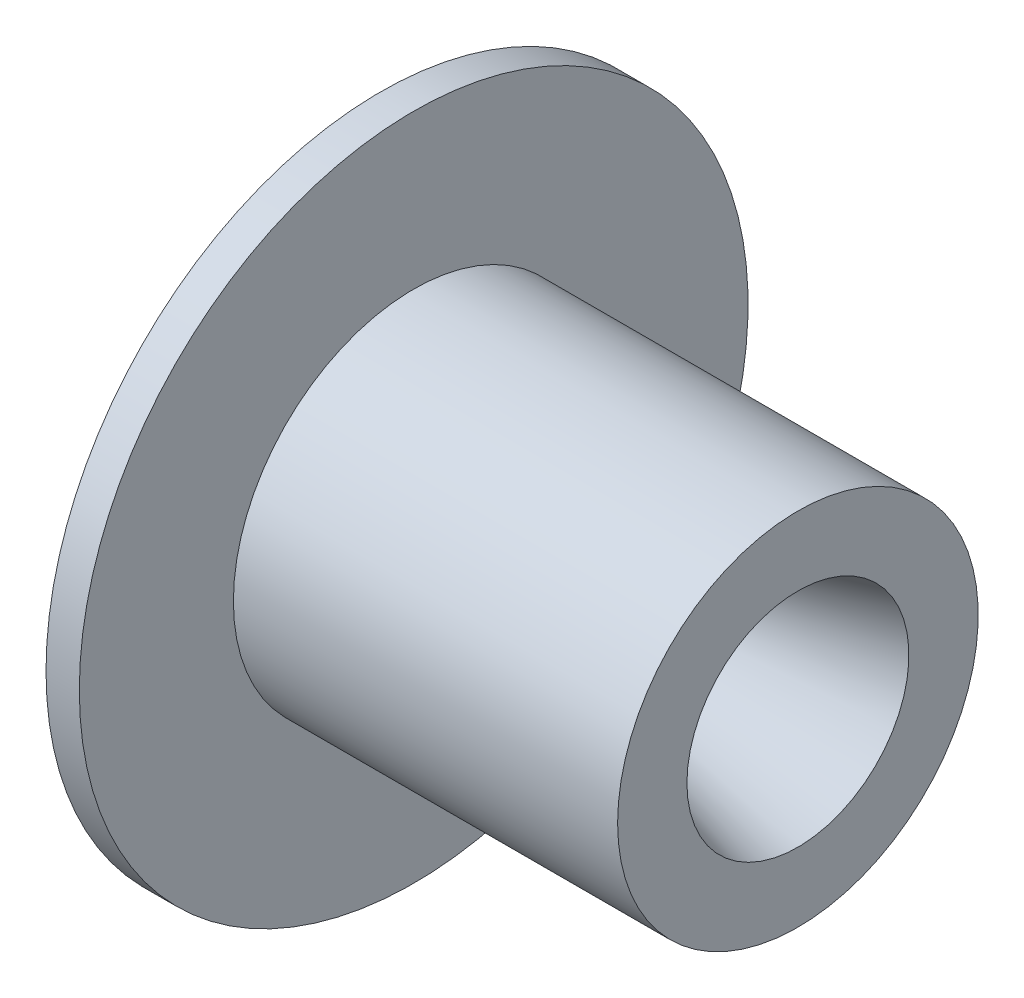
SolidWorks part; units mm, degrees
ref_plane "Front Plane" through (0, 0, 0) normal (0, 0, 1) x (1, 0, 0)
ref_plane "Top Plane" through (0, 0, 0) normal (0, 1, 0) x (1, 0, 0)
ref_plane "Right Plane" through (0, 0, 0) normal (1, 0, 0) x (0, 0, -1)
sketch "Sketch1" plane through (0, 0, 0) normal (0, 0, 1) x (1, 0, 0)
  line L20 (-40.1018, 2.4752) -> (32.997, 2.4752) construction
  line L33 (-4.3532, 9.4212) -> (2.0674, 9.4212)
  line L34 (-4.3532, 9.4212) -> (-24.3532, 27.8752)
  line L37 (-24.3532, 27.8752) -> (-24.3532, 53.4752)
  line L38 (-24.3532, 53.4752) -> (-19.2732, 53.4752)
  line L39 (-19.2732, 53.4752) -> (-19.2732, 29.9752)
  line L43 (39.3282, 29.9752) -> (39.3282, 19.4052)
  line L52 (39.3282, 19.4052) -> (2.0674, 9.4212)
  line L53 (39.3282, 29.9752) -> (-19.2732, 29.9752)
  point P1 (-21.8132, 53.4752)
  point P12 (-4.3532, 9.4212)
  point P24 (2.0674, 9.4212)
  dimension "D1" = 6.946
  dimension "D5" = 5.08
  dimension "D7" = 20
  dimension "D10" = 15
  dimension "D8" = 16.93
  dimension "D3" = 27.5
  dimension "D4" = 51
revolve "Nozzle" add sketch "Sketch1" angle 360 about L20
sketch "Sketch3" plane through (-24.3532, 0, 0) normal (-1, 0, 0) x (0, 0, 1)
  circle A0 centre (0, 42.4802) radius 3.3
  circle A1 centre (0, 2.4752) radius 51 construction
  circle A2 centre (28.2878, 30.763) radius 3.3
  circle A3 centre (40.005, 2.4752) radius 3.3
  circle A4 centre (28.2878, -25.8126) radius 3.3
  circle A5 centre (0, -37.5298) radius 3.3
  circle A6 centre (-28.2878, -25.8126) radius 3.3
  circle A7 centre (-40.005, 2.4752) radius 3.3
  circle A8 centre (-28.2878, 30.763) radius 3.3
  circle A13 centre (0, 2.4752) radius 32.6265 construction
  point P6 (0, 2.4752)
  point P29 (0, 2.4752)
  dimension "D1" = 6.6
  dimension "D2" = 40.005
  dimension "D3" = 8
fillet "Rao inlet radius" radius 20.8 1 edges at (2.0674, 2.4752, 6.946)
fillet "Rao outlet radius" radius 5.3067 1 edges at (-4.3532, 2.4752, 6.946)
sketch "Sketch4" plane through (-24.3532, 0, 0) normal (-1, 0, 0) x (0, 0, 1)
  arc A32 (43.1627, 28.069) -> (23.2989, 28.069) centre (33.2308, 25.9282) ccw
  arc A33 (51.0874, 23.8387) -> (44.9363, 26.1653) centre (33.2308, -14.0768) ccw
  arc A51 (21.5254, 26.1653) -> (19.047, 25.36) centre (33.2308, -14.0768) ccw
  arc A69 (43.1627, 28.069) -> (44.9363, 26.1653) centre (45.6457, 28.6042) ccw
  arc A70 (23.2989, 28.069) -> (21.5254, 26.1653) centre (20.816, 28.6042) cw
  arc A72 (70.0553, 8.7019) -> (56.0095, 22.7477) centre (61.5186, 14.211) ccw
  arc A73 (72.6677, 0.107) -> (69.9633, 6.1017) centre (33.2308, -14.0768) ccw
  arc A74 (53.4093, 22.6557) -> (51.0874, 23.8387) centre (33.2308, -14.0768) ccw
  arc A75 (70.0553, 8.7019) -> (69.9633, 6.1017) centre (72.1895, 7.3246) ccw
  arc A76 (56.0095, 22.7477) -> (53.4093, 22.6557) centre (54.6323, 24.8819) cw
  arc A77 (75.3767, -24.0087) -> (75.3767, -4.1449) centre (73.2358, -14.0768) ccw
  arc A78 (71.1464, -31.9334) -> (73.473, -25.7823) centre (33.2308, -14.0768) ccw
  arc A79 (73.473, -2.3714) -> (72.6677, 0.107) centre (33.2308, -14.0768) ccw
  arc A80 (75.3767, -24.0087) -> (73.473, -25.7823) centre (75.9119, -26.4917) ccw
  arc A81 (75.3767, -4.1449) -> (73.473, -2.3714) centre (75.9119, -1.662) cw
  arc A82 (56.0095, -50.9014) -> (70.0553, -36.8555) centre (61.5186, -42.3646) ccw
  arc A83 (47.4147, -53.5137) -> (53.4093, -50.8093) centre (33.2308, -14.0768) ccw
  arc A84 (69.9633, -34.2553) -> (71.1464, -31.9334) centre (33.2308, -14.0768) ccw
  arc A85 (56.0095, -50.9014) -> (53.4093, -50.8093) centre (54.6323, -53.0355) ccw
  arc A86 (70.0553, -36.8555) -> (69.9633, -34.2553) centre (72.1895, -35.4783) cw
  arc A87 (23.2989, -56.2227) -> (43.1627, -56.2227) centre (33.2308, -54.0818) ccw
  arc A88 (19.047, -53.5137) -> (21.5254, -54.319) centre (33.2308, -14.0768) ccw
  arc A89 (44.9363, -54.319) -> (47.4147, -53.5137) centre (33.2308, -14.0768) ccw
  arc A90 (23.2989, -56.2227) -> (21.5254, -54.319) centre (20.816, -56.7579) ccw
  arc A91 (43.1627, -56.2227) -> (44.9363, -54.319) centre (45.6457, -56.7579) cw
  arc A92 (-3.5937, -36.8555) -> (10.4521, -50.9014) centre (4.943, -42.3646) ccw
  arc A93 (-4.6847, -31.9334) -> (-3.5017, -34.2553) centre (33.2308, -14.0768) ccw
  arc A94 (13.0523, -50.8093) -> (19.047, -53.5137) centre (33.2308, -14.0768) ccw
  arc A95 (-3.5937, -36.8555) -> (-3.5017, -34.2553) centre (-5.7279, -35.4783) ccw
  arc A96 (10.4521, -50.9014) -> (13.0523, -50.8093) centre (11.8294, -53.0355) cw
  arc A97 (-8.915, -4.1449) -> (-8.915, -24.0087) centre (-6.7742, -14.0768) ccw
  arc A98 (-6.206, 0.107) -> (-7.0113, -2.3714) centre (33.2308, -14.0768) ccw
  arc A99 (-7.0113, -25.7823) -> (-4.6847, -31.9334) centre (33.2308, -14.0768) ccw
  arc A100 (-8.915, -4.1449) -> (-7.0113, -2.3714) centre (-9.4502, -1.662) ccw
  arc A101 (-8.915, -24.0087) -> (-7.0113, -25.7823) centre (-9.4502, -26.4917) cw
  arc A102 (10.4521, 22.7477) -> (-3.5937, 8.7019) centre (4.943, 14.211) ccw
  arc A103 (19.047, 25.36) -> (13.0523, 22.6557) centre (33.2308, -14.0768) ccw
  arc A104 (-3.5017, 6.1017) -> (-6.206, 0.107) centre (33.2308, -14.0768) ccw
  arc A105 (10.4521, 22.7477) -> (13.0523, 22.6557) centre (11.8294, 24.8819) ccw
  arc A106 (-3.5937, 8.7019) -> (-3.5017, 6.1017) centre (-5.7279, 7.3246) cw
  point P1 (33.2308, -14.0768)
  point P69 (33.2308, -14.0768)
  point P78 (23.0923, 26.5884)
  dimension "D1" = 8
  dimension "D3" = 41.91
  dimension "D4" = 2.54
  dimension "D2" = 10.16
  dimension "D5" = 40.005
equation "\"radius\"= 1in"
equation "\"Flange\"= 2.35cm"
equation "\"Length\"= 2cm"
equation "\"Flange_Thickness\"= 0.2in"
equation "\"offset\"= 0.625cm"
equation "\"D2@Sketch1\"=\"radius\""
equation "\"throat\"= 0.6946cm"
equation "\"hole_dia\"= 0.66cm"
equation "\"D1@Sketch1\"=\"throat\""
equation "\"D5@Sketch1\"=\"Flange_Thickness\""
equation "\"D7@Sketch1\"=\"Length\""
equation "\"D1@Sketch3\"=\"hole_dia\""
equation "\"D2@Sketch3\"=1.575in"
equation "\"Seal_dia\"= 2.5cm"
equation "\"Seal_depth\"= 0.1cm"
equation "\"Seal_width\"= 0.15cm"
equation "\"Nozzle_angle\"= 15"
equation "\"D10@Sketch1\"=\"Nozzle_angle\""
equation "\"nozzle_length\"= 6.34"
equation "\"bolt_head_dia\"=2.3795"
equation "\"bolt_rad\"= \"radius\" + 0.5 * \"Flange\" + ( ( \"offset\" ^ 2 ) - ( \"Flange_Thickness\" ^ 2 ) ) ^ 0.5cm"
equation "\"scallop_inner_dia\"= 3.3in"
equation "\"exit_rad\"= 1.693cm"
equation "\"D8@Sketch1\"=\"exit_rad\""
equation "\"outside_dia\"= 2.75cm"
equation "\"D3@Sketch1\"=\"outside_dia\""
equation "\"D4@Sketch1\"=\"outside_dia\"+\"Flange\""
equation "\"Scallop_OD\"= 0.8in"
equation "\"D1@Rao outlet radius\" = 2 * 0.382 * \"throat\""
equation "\"D3@Sketch5\"=\"Scallop_OD\"/2"
equation "\"D4@Sketch5\"=\"scallop_inner_dia\"/2"
